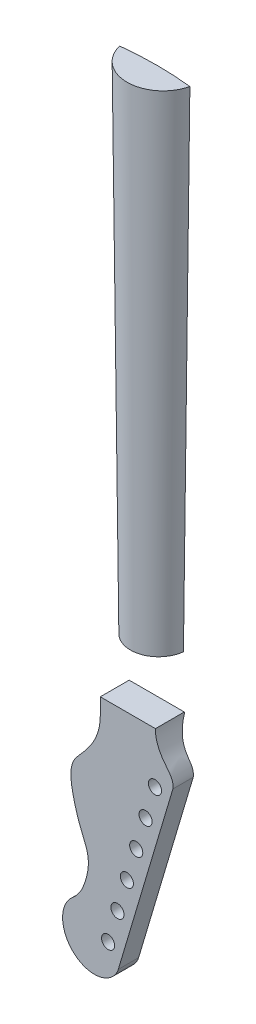
SolidWorks part; units mm, degrees
material "Maple"
ref_plane "Front Plane" through (0, 0, 0) normal (0, 0, 1) x (1, 0, 0)
ref_plane "Top Plane" through (0, 0, 0) normal (0, 1, 0) x (1, 0, 0)
ref_plane "Right Plane" through (0, 0, 0) normal (1, 0, 0) x (0, 0, -1)
sketch "Model" plane through (0, 0, 0) normal (0, 0, 1) x (1, 0, 0)
  line L0 (47.9999, 0) -> (57.149, 660.4)
  line L1 (40.86, 0) -> (46.3494, 660.4)
  line L2 (33.72, 0) -> (35.5498, 660.4)
  line L3 (26.5801, 0) -> (24.7503, 660.4)
  line L4 (19.4401, 0) -> (13.9507, 660.4)
  line L5 (12.3002, 0) -> (3.1511, 660.4)
  line L6 (51.151, 0) -> (60.3001, 660.4)
  line L7 (9.1491, 0) -> (0, 660.4)
  line L8 (51.659, 0) -> (43.9219, 0)
  line L9 (52.1725, 37.0654) -> (44.3327, 37.0654)
  line L10 (52.6572, 72.0505) -> (44.7205, 72.0505)
  line L11 (53.1147, 105.072) -> (45.0865, 105.072)
  line L12 (53.5465, 136.2402) -> (45.4319, 136.2402)
  line L13 (53.954, 165.659) -> (45.7579, 165.659)
  line L14 (54.3387, 193.4267) -> (46.0657, 193.4267)
  line L15 (54.7018, 219.6359) -> (46.3562, 219.6359)
  line L16 (55.0445, 244.3741) -> (46.6304, 244.3741)
  line L17 (55.368, 267.7238) -> (46.8891, 267.7238)
  line L18 (55.6734, 289.763) -> (47.1334, 289.763)
  line L19 (55.9616, 310.5653) -> (47.364, 310.5653)
  line L20 (56.2336, 330.2) -> (47.5816, 330.2)
  line L21 (56.4903, 348.7327) -> (47.787, 348.7327)
  line L22 (56.7327, 366.2252) -> (47.9808, 366.2252)
  line L23 (56.9614, 382.736) -> (48.1638, 382.736)
  line L24 (57.1773, 398.3201) -> (48.3365, 398.3201)
  line L25 (57.3811, 413.0295) -> (48.4996, 413.0295)
  line L26 (57.5734, 426.9133) -> (48.6534, 426.9133)
  line L27 (57.755, 440.0179) -> (48.7987, 440.0179)
  line L28 (57.9263, 452.387) -> (48.9358, 452.387)
  line L29 (58.0881, 464.0619) -> (49.0652, 464.0619)
  line L30 (58.2407, 475.0815) -> (49.1873, 475.0815)
  line L31 (58.3848, 485.4826) -> (49.3026, 485.4826)
  line L32 (58.5208, 495.3) -> (49.4114, 495.3)
  line L33 (44.9379, 0) -> (36.782, 0)
  line L34 (45.3487, 37.0654) -> (36.9874, 37.0654)
  line L35 (45.7365, 72.0505) -> (37.1813, 72.0505)
  line L36 (46.1025, 105.072) -> (37.3643, 105.072)
  line L37 (46.4479, 136.2402) -> (37.537, 136.2402)
  line L38 (46.7739, 165.659) -> (37.7, 165.659)
  line L39 (47.0817, 193.4267) -> (37.8539, 193.4267)
  line L40 (47.3722, 219.6359) -> (37.9991, 219.6359)
  line L41 (47.6464, 244.3741) -> (38.1362, 244.3741)
  line L42 (47.9051, 267.7238) -> (38.2656, 267.7238)
  line L43 (48.1494, 289.763) -> (38.3877, 289.763)
  line L44 (48.38, 310.5653) -> (38.503, 310.5653)
  line L45 (48.5976, 330.2) -> (38.6118, 330.2)
  line L46 (48.803, 348.7327) -> (38.7145, 348.7327)
  line L47 (48.9968, 366.2252) -> (38.8114, 366.2252)
  line L48 (49.1798, 382.736) -> (38.9029, 382.736)
  line L49 (49.3525, 398.3201) -> (38.9893, 398.3201)
  line L50 (49.5156, 413.0295) -> (39.0708, 413.0295)
  line L51 (49.6694, 426.9133) -> (39.1478, 426.9133)
  line L52 (49.8147, 440.0179) -> (39.2204, 440.0179)
  line L53 (49.9518, 452.387) -> (39.2889, 452.387)
  line L54 (50.0812, 464.0619) -> (39.3536, 464.0619)
  line L55 (50.2033, 475.0815) -> (39.4147, 475.0815)
  line L56 (50.3186, 485.4826) -> (39.4723, 485.4826)
  line L57 (50.4274, 495.3) -> (39.5267, 495.3)
  line L58 (37.798, 0) -> (29.6421, 0)
  line L59 (38.0034, 37.0654) -> (29.6421, 37.0654)
  line L60 (38.1973, 72.0505) -> (29.6421, 72.0505)
  line L61 (38.3803, 105.072) -> (29.6421, 105.072)
  line L62 (38.553, 136.2402) -> (29.6421, 136.2402)
  line L63 (38.716, 165.659) -> (29.6421, 165.659)
  line L64 (38.8699, 193.4267) -> (29.6421, 193.4267)
  line L65 (39.0151, 219.6359) -> (29.6421, 219.6359)
  line L66 (39.1522, 244.3741) -> (29.6421, 244.3741)
  line L67 (39.2816, 267.7238) -> (29.6421, 267.7238)
  line L68 (39.4037, 289.763) -> (29.6421, 289.763)
  line L69 (39.519, 310.5653) -> (29.6421, 310.5653)
  line L70 (39.6278, 330.2) -> (29.6421, 330.2)
  line L71 (39.7305, 348.7327) -> (29.6421, 348.7327)
  line L72 (39.8274, 366.2252) -> (29.6421, 366.2252)
  line L73 (39.9189, 382.736) -> (29.6421, 382.736)
  line L74 (40.0053, 398.3201) -> (29.6421, 398.3201)
  line L75 (40.0868, 413.0295) -> (29.6421, 413.0295)
  line L76 (40.1638, 426.9133) -> (29.6421, 426.9133)
  line L77 (40.2364, 440.0179) -> (29.6421, 440.0179)
  line L78 (40.3049, 452.387) -> (29.6421, 452.387)
  line L79 (40.3696, 464.0619) -> (29.6421, 464.0619)
  line L80 (40.4307, 475.0815) -> (29.6421, 475.0815)
  line L81 (40.4883, 485.4826) -> (29.6421, 485.4826)
  line L82 (40.5427, 495.3) -> (29.6421, 495.3)
  line L83 (30.6581, 0) -> (22.5021, 0)
  line L84 (30.6581, 37.0654) -> (22.2967, 37.0654)
  line L85 (30.6581, 72.0505) -> (22.1028, 72.0505)
  line L86 (30.6581, 105.072) -> (21.9199, 105.072)
  line L87 (30.6581, 136.2402) -> (21.7471, 136.2402)
  line L88 (30.6581, 165.659) -> (21.5841, 165.659)
  line L89 (30.6581, 193.4267) -> (21.4302, 193.4267)
  line L90 (30.6581, 219.6359) -> (21.285, 219.6359)
  line L91 (30.6581, 244.3741) -> (21.1479, 244.3741)
  line L92 (30.6581, 267.7238) -> (21.0185, 267.7238)
  line L93 (30.6581, 289.763) -> (20.8964, 289.763)
  line L94 (30.6581, 310.5653) -> (20.7811, 310.5653)
  line L95 (30.6581, 330.2) -> (20.6723, 330.2)
  line L96 (30.6581, 348.7327) -> (20.5696, 348.7327)
  line L97 (30.6581, 366.2252) -> (20.4727, 366.2252)
  line L98 (30.6581, 382.736) -> (20.3812, 382.736)
  line L99 (30.6581, 398.3201) -> (20.2948, 398.3201)
  line L100 (30.6581, 413.0295) -> (20.2133, 413.0295)
  line L101 (30.6581, 426.9133) -> (20.1364, 426.9133)
  line L102 (30.6581, 440.0179) -> (20.0637, 440.0179)
  line L103 (30.6581, 452.387) -> (19.9952, 452.387)
  line L104 (30.6581, 464.0619) -> (19.9305, 464.0619)
  line L105 (30.6581, 475.0815) -> (19.8694, 475.0815)
  line L106 (30.6581, 485.4826) -> (19.8118, 485.4826)
  line L107 (30.6581, 495.3) -> (19.7574, 495.3)
  line L108 (23.5181, 0) -> (15.3622, 0)
  line L109 (23.3127, 37.0654) -> (14.9514, 37.0654)
  line L110 (23.1188, 72.0505) -> (14.5636, 72.0505)
  line L111 (22.9359, 105.072) -> (14.1977, 105.072)
  line L112 (22.7631, 136.2402) -> (13.8522, 136.2402)
  line L113 (22.6001, 165.659) -> (13.5262, 165.659)
  line L114 (22.4462, 193.4267) -> (13.2184, 193.4267)
  line L115 (22.301, 219.6359) -> (12.9279, 219.6359)
  line L116 (22.1639, 244.3741) -> (12.6538, 244.3741)
  line L117 (22.0345, 267.7238) -> (12.395, 267.7238)
  line L118 (21.9124, 289.763) -> (12.1507, 289.763)
  line L119 (21.7971, 310.5653) -> (11.9202, 310.5653)
  line L120 (21.6883, 330.2) -> (11.7025, 330.2)
  line L121 (21.5856, 348.7327) -> (11.4971, 348.7327)
  line L122 (21.4887, 366.2252) -> (11.3033, 366.2252)
  line L123 (21.3972, 382.736) -> (11.1203, 382.736)
  line L124 (21.3108, 398.3201) -> (10.9476, 398.3201)
  line L125 (21.2293, 413.0295) -> (10.7845, 413.0295)
  line L126 (21.1524, 426.9133) -> (10.6307, 426.9133)
  line L127 (21.0797, 440.0179) -> (10.4854, 440.0179)
  line L128 (21.0112, 452.387) -> (10.3483, 452.387)
  line L129 (20.9465, 464.0619) -> (10.2189, 464.0619)
  line L130 (20.8854, 475.0815) -> (10.0968, 475.0815)
  line L131 (20.8278, 485.4826) -> (9.9815, 485.4826)
  line L132 (20.7734, 495.3) -> (9.8727, 495.3)
  line L133 (16.3782, 0) -> (8.6411, 0)
  line L134 (15.9674, 37.0654) -> (8.1276, 37.0654)
  line L135 (15.5796, 72.0505) -> (7.6429, 72.0505)
  line L136 (15.2137, 105.072) -> (7.1854, 105.072)
  line L137 (14.8682, 136.2402) -> (6.7536, 136.2402)
  line L138 (14.5422, 165.659) -> (6.3461, 165.659)
  line L139 (14.2344, 193.4267) -> (5.9614, 193.4267)
  line L140 (13.9439, 219.6359) -> (5.5983, 219.6359)
  line L141 (13.6698, 244.3741) -> (5.2556, 244.3741)
  line L142 (13.411, 267.7238) -> (4.9321, 267.7238)
  line L143 (13.1667, 289.763) -> (4.6267, 289.763)
  line L144 (12.9362, 310.5653) -> (4.3386, 310.5653)
  line L145 (12.7185, 330.2) -> (4.0665, 330.2)
  line L146 (12.5131, 348.7327) -> (3.8098, 348.7327)
  line L147 (12.3193, 366.2252) -> (3.5675, 366.2252)
  line L148 (12.1363, 382.736) -> (3.3387, 382.736)
  line L149 (11.9636, 398.3201) -> (3.1228, 398.3201)
  line L150 (11.8005, 413.0295) -> (2.919, 413.0295)
  line L151 (11.6467, 426.9133) -> (2.7267, 426.9133)
  line L152 (11.5014, 440.0179) -> (2.5451, 440.0179)
  line L153 (11.3643, 452.387) -> (2.3738, 452.387)
  line L154 (11.2349, 464.0619) -> (2.212, 464.0619)
  line L155 (11.1128, 475.0815) -> (2.0594, 475.0815)
  line L156 (10.9975, 485.4826) -> (1.9153, 485.4826)
  line L157 (10.8887, 495.3) -> (1.7793, 495.3)
ref_plane "Plane1" through (0, 37.07, 0) normal (0, 1, 0) x (1, 0, 0)
ref_plane "Plane2" through (0, 413.03, 0) normal (0, 1, 0) x (1, 0, 0)
sketch "Sketch2" plane through (0, 37.07, 0) normal (0, 1, 0) x (1, 0, 0)
  line L0 (22.5021, 0) -> (37.798, 0) construction
  line L4 (30.6581, 0) -> (22.5021, 0) construction
  line L5 (30.6581, 0) -> (22.2967, 0) construction
  line L6 (37.798, 0) -> (29.6421, 0) construction
  line L7 (30.1501, 0) -> (30.1501, -241.3) construction
  line L8 (30.1501, 0) -> (30.1501, -20) construction
  line L9 (30.1501, 0) -> (30.1501, 60) construction
  line L10 (8.7751, 0) -> (51.5251, 0) construction
  arc A0 (51.4416, -0.9412) -> (8.8585, -0.9412) centre (30.1501, -241.3) ccw
  arc A1 (8.7751, 0) -> (8.8585, -0.9412) centre (30.1501, 1.4219) ccw construction
  arc A3 (8.8585, -0.9412) -> (51.4416, -0.9412) centre (30.1501, 1.4219) ccw
  point P17 (30.1501, 0)
  dimension "D1" = 241.3
  dimension "D2" = 20
  dimension "D3" = 60
  dimension "D4" = 42.75
sketch "Sketch4" plane through (0, 413.03, 0) normal (0, 1, 0) x (1, 0, 0)
  line L0 (37.798, 0) -> (22.5021, 0) construction
  line L1 (37.798, 0) -> (29.6421, 0) construction
  line L2 (44.9379, 0) -> (36.782, 0) construction
  line L3 (30.6581, 0) -> (22.5021, 0) construction
  line L4 (30.6581, 0) -> (22.2967, 0) construction
  line L5 (30.1501, 0) -> (30.1501, -241.3) construction
  line L6 (30.1501, 0) -> (30.1501, -22.6) construction
  line L7 (57.2001, 0) -> (3.1001, 0) construction
  circle A0 centre (30.1501, -241.3) radius 241.3 construction
  arc A1 (57.2001, 0) -> (56.8889, -1.4861) centre (30.1501, 4.8875) cw construction
  arc A2 (3.4112, -1.4861) -> (56.8889, -1.4861) centre (30.1501, -241.3) cw
  arc A3 (3.4112, -1.4861) -> (3.1001, 0) centre (30.1501, 4.8875) cw construction
  arc A4 (56.8889, -1.4861) -> (3.4112, -1.4861) centre (30.1501, 4.8875) cw
  point P18 (30.1501, 0)
  dimension "D1" = 241.3
  dimension "D2" = 22.6
  dimension "D3" = 54.1
loft "Loft1" add profiles "Sketch4", "Sketch2"
sketch "Sketch5" plane through (0, 0, 0) normal (0, 0, 1) x (1, 0, 0)
  line L0 (51.151, 0) -> (51.151, -3.25) construction
  line L1 (51.151, -3.25) -> (9.1491, -3.25) construction
  line L2 (9.1491, -3.25) -> (9.1491, 0) construction
  line L3 (51.151, 0) -> (9.1491, 0) construction
  line L10 (47.9999, 0) -> (47.9999, -42) construction
  line L11 (40.86, 0) -> (40.86, -66) construction
  line L12 (33.72, 0) -> (33.72, -90) construction
  line L13 (26.5801, 0) -> (26.5801, -114) construction
  line L14 (19.4401, 0) -> (19.4401, -138) construction
  line L15 (12.3002, 0) -> (12.3002, -162) construction
  dimension "D1" = 3.25
  dimension "D2" = 42
  dimension "D3" = 66
  dimension "D4" = 90
  dimension "D5" = 114
  dimension "D6" = 138
  dimension "D7" = 162
sketch "Sketch7" plane through (0, 0, 0) normal (0, 0, 1) x (1, 0, 0)
  line L0 (47.9999, -42) -> (50.7999, -42) construction
  line L1 (40.86, -66) -> (43.66, -66) construction
  line L2 (33.72, -90) -> (36.52, -90) construction
  line L3 (26.5801, -114) -> (29.3801, -114) construction
  line L4 (19.4401, -138) -> (22.2401, -138) construction
  line L5 (12.3002, -162) -> (15.1002, -162) construction
  line L6 (50.7999, -42) -> (15.1002, -162) construction
  line L7 (61.8225, -45.2792) -> (26.1228, -165.2792)
  line L8 (61.8225, -45.2792) -> (64.4679, -36.3869)
  line L9 (26.1228, -165.2792) -> (22.17, -178.5661)
  line L10 (9.1491, -3.25) -> (9.1491, -15.8462)
  line L11 (51.151, -3.25) -> (9.1491, -3.25)
  circle A0 centre (50.7999, -42) radius 5
  circle A6 centre (43.66, -66) radius 5
  circle A7 centre (36.52, -90) radius 5
  circle A8 centre (29.3801, -114) radius 5
  circle A9 centre (22.2401, -138) radius 5
  circle A10 centre (15.1002, -162) radius 5
  circle A11 centre (50.7999, -42) radius 7 construction
  circle A12 centre (43.66, -66) radius 7 construction
  circle A13 centre (36.52, -90) radius 7 construction
  circle A14 centre (29.3801, -114) radius 7 construction
  circle A15 centre (22.2401, -138) radius 7 construction
  circle A16 centre (15.1002, -162) radius 7 construction
  arc A17 (-12.1507, -146.4192) -> (-6.0074, -139.1839) centre (-31.6598, -123.629) ccw
  ellipse E0 centre (2.8278, -165.1094) end of major axis (14.6602, -186.0066) minor radius 21.8622 (-12.1507, -146.4192) -> (22.17, -178.5661) ccw
  spline S2 degree 3 poles (51.151, -3.25) (50.9376, -10.7673) (56.4838, -22.0007) (65.2963, -30.5662) (64.4679, -36.3869) knots 0 0 0 0 0.598162 1 1 1 1
  spline S3 degree 3 poles (9.1491, -15.8462) (9.1416, -28.5012) (1.4204, -41.2547) (-15.1493, -58.1713) (-12.0269, -78.7636) (-6.3018, -97.3659) (3.4284, -117.1529) (-3.2556, -134.6457) (-6.0074, -139.1839) knots 0 0 0 0 0.241122 0.31589 0.476811 0.625348 0.735304 0.929975 0.929975 0.929975 0.929975
  point P32 (-6.6579, -142.6678)
  point P33 (0, 0)
  point P37 (-16.1964, -175.8813)
  point P38 (-6.0074, -139.1839)
  dimension "D7" = 10
  dimension "D8" = 10
  dimension "D9" = 10
  dimension "D10" = 10
  dimension "D11" = 10
  dimension "D12" = 10
  dimension "D13" = 11.5
  dimension "D14" = 30
  dimension "D1" = 2.8
  dimension "D2" = 2.8
  dimension "D3" = 2.8
  dimension "D4" = 2.8
  dimension "D5" = 2.8
  dimension "D6" = 2.8
extrude "Boss-Extrude1" add sketch "Sketch7" along normal blind 22 separate body
sketch "Sketch9" plane through (0, 0, 0) normal (1, 0, 0) x (0, 0, -1)
  line L0 (0, -188.6196) -> (-6.5, -188.6196)
  line L1 (-22, -188.6196) -> (0, -188.6196) construction
  line L2 (-6.5, -188.6196) -> (-6.5, -21.6831)
  line L3 (-22, -3.25) -> (0, -3.25) construction
  line L4 (-6.5, -3.25) -> (0, -3.25) construction
  line L6 (0, -3.25) -> (0, -4.75) construction
  line L7 (0, -4.75) -> (-6.5, -21.6831)
  line L8 (-6.5, -21.6831) -> (-6.5, -3.25) construction
  line L9 (0, -4.75) -> (0, -188.6196)
  point P10 (-6.5, -21.6093)
  point P13 (-2.4341, -19.6214)
  point P14 (0, -4.138)
  dimension "D1" = 6.5
  dimension "D2" = 1.5
extrude "Cut-Extrude1" cut sketch "Sketch9" against normal blind 47 and the other way blind 89 contours L9 L7 L2 L0 region at (0, -100.8499, 3.1977)
fillet "Fillet1" radius 35 1 edges at (33.1406, -21.6831, 6.5)
fillet "Fillet2" radius 15 1 edges at (22.17, -178.5661, 14.25)
